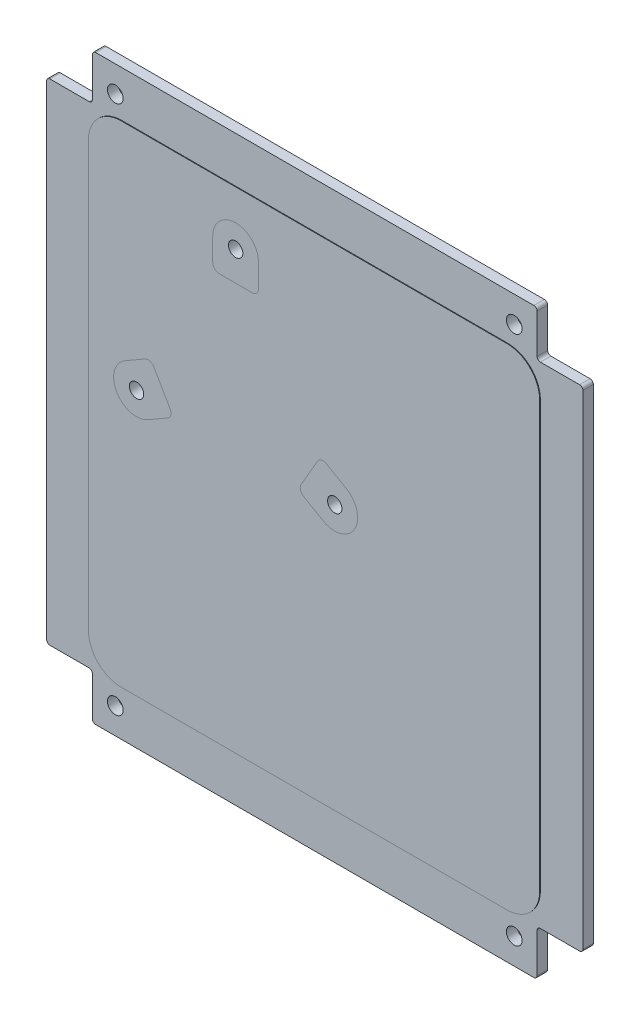
SolidWorks part; units mm, degrees
material "PET"
ref_plane "Front Plane" through (0, 0, 0) normal (0, 0, 1) x (1, 0, 0)
ref_plane "Top Plane" through (0, 0, 0) normal (0, 1, 0) x (1, 0, 0)
ref_plane "Right Plane" through (0, 0, 0) normal (1, 0, 0) x (0, 0, -1)
sketch "Sketch1" plane through (0, 0, 0) normal (0, 0, 1) x (1, 0, 0)
  line L0 (-34, 44) -> (-34, 38)
  line L1 (-33.5, -44.5) -> (33.5, -44.5)
  line L2 (-41, 37) -> (-41, -37)
  line L3 (-33.5, 44.5) -> (33.5, 44.5)
  line L4 (41, -37) -> (41, 37)
  line L5 (34, -44) -> (34, -38)
  line L6 (34.5, -37.5) -> (40.5, -37.5)
  line L7 (-34.5, 37.5) -> (-40.5, 37.5)
  line L8 (34, 44) -> (34, 38)
  line L9 (34.5, 37.5) -> (40.5, 37.5)
  line L10 (-40.5, -37.5) -> (-34.5, -37.5)
  line L11 (-34, -38) -> (-34, -44)
  line L12 (-34.5, -38) -> (34.5, 38) construction
  line L13 (34.5, -38) -> (-34.5, 38) construction
  arc A0 (-33.5, 44.5) -> (-34, 44) centre (-33.5, 44) ccw
  arc A1 (33.5, 44.5) -> (34, 44) centre (33.5, 44) cw
  arc A2 (34, 38) -> (34.5, 37.5) centre (34.5, 38) ccw
  arc A3 (40.5, 37.5) -> (41, 37) centre (40.5, 37) cw
  arc A4 (33.5, -44.5) -> (34, -44) centre (33.5, -44) ccw
  arc A5 (34.5, -37.5) -> (34, -38) centre (34.5, -38) ccw
  arc A6 (40.5, -37.5) -> (41, -37) centre (40.5, -37) ccw
  arc A7 (-34, -44) -> (-33.5, -44.5) centre (-33.5, -44) ccw
  arc A8 (-34, -38) -> (-34.5, -37.5) centre (-34.5, -38) ccw
  arc A9 (-41, -37) -> (-40.5, -37.5) centre (-40.5, -37) ccw
  arc A10 (-40.5, 37.5) -> (-41, 37) centre (-40.5, 37) ccw
  arc A11 (-34.5, 37.5) -> (-34, 38) centre (-34.5, 38) ccw
  point P0 (0, 0)
  dimension "D4" = 0.5
  dimension "D1" = 7
  dimension "D2" = 7
  dimension "D3" = 7
  dimension "D5" = 7
  dimension "D6" = 7
  dimension "D7" = 7
  dimension "D8" = 7
  dimension "D9" = 7
  dimension "D10" = 89
  dimension "D11" = 82
extrude "Boss-Extrude1" add sketch "Sketch1" along normal blind 1.6
sketch "Esboço1" plane through (0, 0, 1.6) normal (0, 0, 1) x (1, 0, 0)
  line L1 (-29.5, -37.5) -> (29.5, -37.5)
  line L2 (-34.5, -32.5) -> (-34.5, 32.5)
  line L3 (-29.5, 37.5) -> (29.5, 37.5)
  line L4 (34.5, -32.5) -> (34.5, 32.5)
  line L5 (-29.5, -32.5) -> (29.5, 32.5) construction
  line L6 (-29.5, 32.5) -> (29.5, -32.5) construction
  arc A0 (-34.5, 32.5) -> (-29.5, 37.5) centre (-29.5, 32.5) cw
  arc A1 (29.5, 37.5) -> (34.5, 32.5) centre (29.5, 32.5) cw
  arc A2 (34.5, -32.5) -> (29.5, -37.5) centre (29.5, -32.5) cw
  arc A3 (-29.5, -37.5) -> (-34.5, -32.5) centre (-29.5, -32.5) cw
  point P0 (0, 0)
  dimension "D1" = 5
  dimension "D2" = 69
  dimension "D3" = 75
extrude "Boss-Extrude2" add sketch "Esboço1" along normal blind 0.1
hole_wizard "M2 Hole1-FixingStructure" positions "Sketch3" profile "Sketch2" hole size "M2" standard "DIN"
sketch "Sketch3" plane through (0, 0, 0) normal (0, 0, -1) x (-1, 0, 0)
  line L0 (-33.5, 44.5) -> (33.5, 44.5) construction
  line L1 (33.5, -44.5) -> (-33.5, -44.5) construction
  line L2 (-41, -37) -> (-41, 37) construction
  line L3 (41, 37) -> (41, -37) construction
  point P0 (-30.5, 40.5)
  point P2 (30.5, 40.5)
  point P4 (-30.5, -40.5)
  point P6 (30.5, -40.5)
  dimension "D1" = 4
  dimension "D2" = 4
  dimension "D3" = 10.5
  dimension "D4" = 10.5
sketch "Sketch2" plane through (30.5, 40.5, 0) normal (1, 0, 0) x (0, 1, 0)
  line L0 (0, 0) -> (0, 200.721)
  line L1 (0, 200.721) -> (1.2, 200)
  line L2 (1.2, 200) -> (1.2, 0)
  line L5 (1.2, 0) -> (0, 0)
  line L10 (0, 200.721) -> (-1.2, 200) construction
  line L11 (0, -6.35) -> (0, 107.95) construction
  dimension "Hole Dia." = 2.4
  dimension "Hole Depth" = 200
  dimension "Drill Angle" = 118
sketch "Sketch4" plane through (0, 0, 1.7) normal (0, 0, 1) x (1, 0, 0)
  circle A0 centre (-27.1554, 3) radius 1.1 construction
  circle A1 centre (3.1554, 3) radius 1.1 construction
  circle A2 centre (-12, 29.25) radius 1.1 construction
  circle A3 centre (-27.1554, 3) radius 1.1
  circle A4 centre (3.1554, 3) radius 1.1
  circle A5 centre (-12, 29.25) radius 1.1
extrude "Cut-Extrude1" cut sketch "Sketch4" against normal up to surface (1.7 mm away) up to face at (29.3, 40.5, 0)
sketch "Sketch5" plane through (0, 0, 1.7) normal (0, 0, 1) x (1, 0, 0)
  line L6 (-15.5, 25.75) -> (-15.5, 29.25)
  line L7 (-23.2404, 1.2189) -> (-25.4054, -0.0311)
  line L8 (-28.9054, 6.0311) -> (-26.7404, 7.2811)
  line L9 (-22.3744, 1.7189) -> (-25.4054, -0.0311)
  line L10 (-28.9054, 6.0311) -> (-25.8744, 7.7811)
  line L11 (-24.5083, 7.4151) -> (-22.0083, 3.0849)
  line L12 (-24.5083, 7.4151) -> (-22.0083, 3.0849)
  line L13 (-8.5, 29.25) -> (-8.5, 25.75)
  line L14 (-9.5, 24.75) -> (-14.5, 24.75)
  line L15 (1.8744, 7.7811) -> (4.9054, 6.0311)
  line L16 (1.4054, -0.0311) -> (-1.6256, 1.7189)
  line L17 (-1.9917, 3.0849) -> (0.5083, 7.4151)
  arc A2 (-25.8744, 7.7811) -> (-24.5083, 7.4151) centre (-25.3744, 6.9151) cw
  arc A3 (-28.9054, 6.0311) -> (-25.4054, -0.0311) centre (-27.1554, 3) ccw
  arc A4 (-28.9054, 6.0311) -> (-25.4054, -0.0311) centre (-27.1554, 3) ccw
  arc A5 (-22.3744, 1.7189) -> (-22.0083, 3.0849) centre (-22.8744, 2.5849) ccw
  circle A6 centre (-12, 11.75) radius 10 construction
  arc A7 (-8.5, 25.75) -> (-9.5, 24.75) centre (-9.5, 25.75) cw
  arc A8 (-8.5, 29.25) -> (-15.5, 29.25) centre (-12, 29.25) ccw
  arc A9 (-15.5, 25.75) -> (-14.5, 24.75) centre (-14.5, 25.75) ccw
  arc A10 (-1.6256, 1.7189) -> (-1.9917, 3.0849) centre (-1.1256, 2.5849) cw
  arc A11 (1.4054, -0.0311) -> (4.9054, 6.0311) centre (3.1554, 3) ccw
  arc A12 (1.8744, 7.7811) -> (0.5083, 7.4151) centre (1.3744, 6.9151) ccw
  point P13 (-12, 11.75)
  point P37 (-12, 11.75)
  dimension "D3" = 1
  dimension "D1" = 1
  dimension "D2" = 1
  dimension "D4" = 3
split line "Split Line1"
